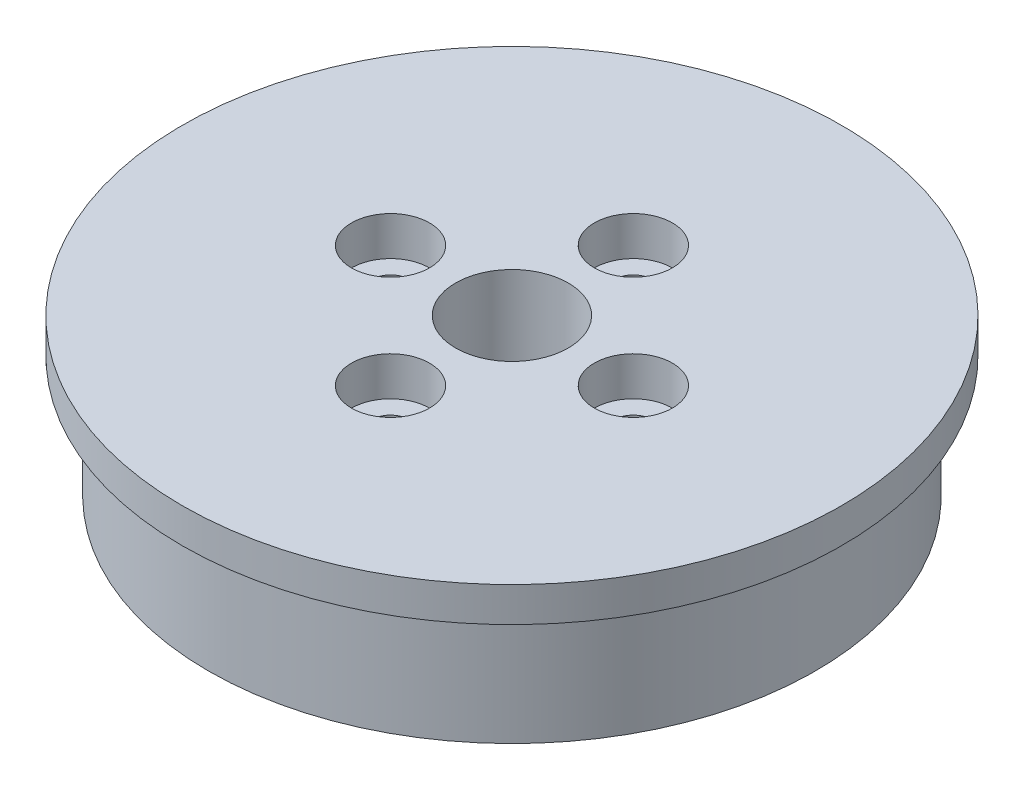
SolidWorks part; units mm, degrees
ref_plane "Front" through (0, 0, 0) normal (0, 0, 1) x (1, 0, 0)
ref_plane "Top" through (0, 0, 0) normal (0, 1, 0) x (1, 0, 0)
ref_plane "Right" through (0, 0, 0) normal (1, 0, 0) x (0, 0, -1)
sketch "Эскиз1" plane through (0, 0, 0) normal (0, 1, 0) x (1, 0, 0)
  circle A0 centre (0, 0) radius 19
  dimension "D1" = 38
extrude "Бобышка-Вытянуть1" add sketch "Эскиз1" along normal blind 10.45
sketch "Эскиз2" plane through (0, 0, 0) normal (0, 1, 0) x (1, 0, 0)
  circle A0 centre (0, 0) radius 10
  circle A1 centre (0, 0) radius 17.5
  circle A2 centre (0, 0) radius 35.8784
  dimension "D1" = 35
  dimension "D2" = 20
extrude "Вырез-Вытянуть1" cut sketch "Эскиз2" along normal blind 1.45 contours A1 A0 | A2 A1 region at (-17.005, 0, 0) region at (-34.8636, 0, 0)
extrude "Вырез-Вытянуть2" cut sketch "Эскиз2<3>" along normal blind 8.45 contours A2 A1 region at (-34.8636, 0, 0)
sketch "Эскиз2<3>" plane through (0, 0, 0) normal (0, 1, 0) x (1, 0, 0) same geometry as "Эскиз2"
sketch "Эскиз3" plane through (0, 0, 0) normal (0, 1, 0) x (1, 0, 0)
  circle A0 centre (0, 0) radius 7 construction
  circle A1 centre (0, 0) radius 3.25
  circle A2 centre (0, 7) radius 1.1
  circle A3 centre (-7, 0) radius 1.1
  circle A4 centre (0, -7) radius 1.1
  circle A5 centre (7, 0) radius 1.1
  circle A6 centre (0, 7) radius 2.25
  circle A7 centre (7, 0) radius 2.25
  circle A8 centre (0, -7) radius 2.25
  circle A9 centre (-7, 0) radius 2.25
  dimension "D1" = 6.5
  dimension "D2" = 14
  dimension "D3" = 2.2
  dimension "D4" = 2.2
  dimension "D5" = 2.2
  dimension "D6" = 2.2
  dimension "D7" = 4.5
  dimension "D8" = 4.5
  dimension "D9" = 4.5
  dimension "D10" = 4.5
extrude "Вырез-Вытянуть3" cut sketch "Эскиз3" along normal through all contours A4 | A3 | A1 | A2 | A5
extrude "Вырез-Вытянуть4" cut sketch "Эскиз3<3>" along normal through all from offset 8.2 contours A9 | A6 | A7 | A8
sketch "Эскиз3<3>" plane through (0, 0, 0) normal (0, 1, 0) x (1, 0, 0) same geometry as "Эскиз3"
sketch "Эскиз4" plane through (0, 0, 0) normal (0, 1, 0) x (1, 0, 0)
  circle A0 centre (0, 0) radius 10
  circle A1 centre (0, 0) radius 16
  dimension "D1" = 32
  dimension "D2" = 20
extrude "Вырез-Вытянуть5" cut sketch "Эскиз4" along normal blind 2.2
sketch "Эскиз5" plane through (0, 0, 0) normal (0, 1, 0) x (1, 0, 0)
  circle A0 centre (0, 0) radius 4.5
extrude "Вырез-Вытянуть6" cut sketch "Эскиз5" along normal blind 2
